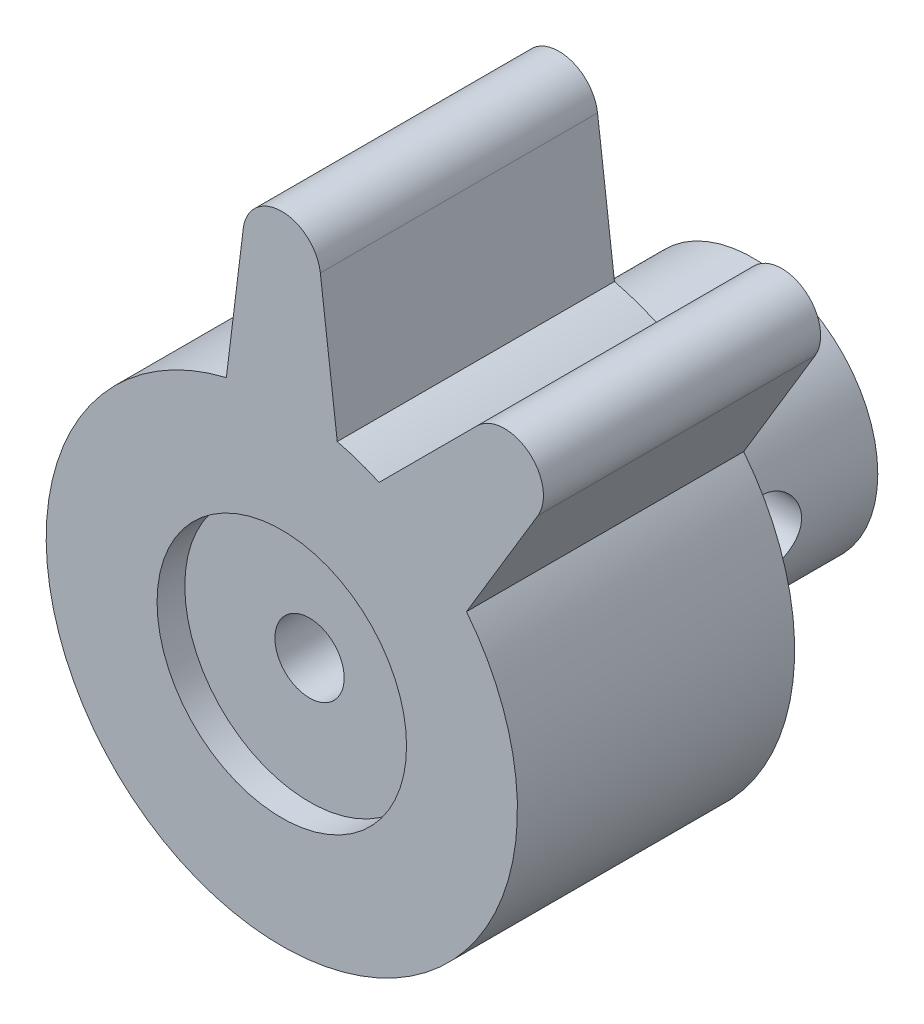
SolidWorks part; units mm, degrees
ref_plane "Front Plane" through (0, 0, 0) normal (0, 0, 1) x (1, 0, 0)
ref_plane "Top Plane" through (0, 0, 0) normal (0, 1, 0) x (1, 0, 0)
ref_plane "Right Plane" through (0, 0, 0) normal (1, 0, 0) x (0, 0, -1)
sketch "Sketch1" plane through (0, 0, 0) normal (0, 0, 1) x (1, 0, 0)
  line L0 (0, 0) -> (0, 51.188) construction
  line L1 (-2, 8.2614) -> (-1.3907, 13.2241)
  line L2 (2, 8.2614) -> (1.3907, 13.2241)
  line L3 (0, 0) -> (22.4184, 65.1077) construction
  line L4 (6.6622, 5.2787) -> (9.2374, 9.5646)
  line L5 (0, 0) -> (31.5145, 40.3367) construction
  line L6 (3.5102, 7.7414) -> (7.0457, 11.2769)
  circle A0 centre (0, 0) radius 8.5
  circle A1 centre (0, 0) radius 1.25
  arc A2 (-1.3907, 13.2241) -> (1.3907, 13.2241) centre (0, 13.0533) cw
  arc A3 (9.2374, 9.5646) -> (7.0457, 11.2769) centre (8.0364, 10.2862) ccw
  circle A4 centre (0, 0) radius 12 construction
  dimension "D1" = 24
  dimension "D2" = 17
  dimension "D3" = 2.5
  dimension "D4" = 7
  dimension "D7" = 5
  dimension "D5" = 4
  dimension "D6" = 19
extrude "Boss-Extrude1" add sketch "Sketch1" along normal blind 10 contours A0 A1 | A2 L1 A0 L2 | A0 region at (0, 11.1065, 0) region at (0, 8.2596, 0) region at (6.8378, 8.752, 0)
sketch "Sketch5" plane through (0, 0, 0) normal (0, 0, -1) x (-1, 0, 0)
  circle A0 centre (0, 0) radius 3
  circle A1 centre (0, 0) radius 4.5
  dimension "D1" = 9
  dimension "D2" = 6
extrude "Boss-Extrude3" add sketch "Sketch5" along normal blind 7
sketch "Sketch6" plane through (0, 0, 0) normal (1, 0, 0) x (0, 0, -1)
  circle A0 centre (3, 0) radius 1.25
  dimension "D1" = 2.5
  dimension "D2" = 3
extrude "Cut-Extrude1" cut sketch "Sketch6" against normal through all both and the other way through all
sketch "Sketch8" plane through (0, 0, 10) normal (0, 0, 1) x (1, 0, 0)
  circle A0 centre (0, 0) radius 4.5
  dimension "D1" = 9
extrude "Cut-Extrude2" cut sketch "Sketch8" against normal blind 1
